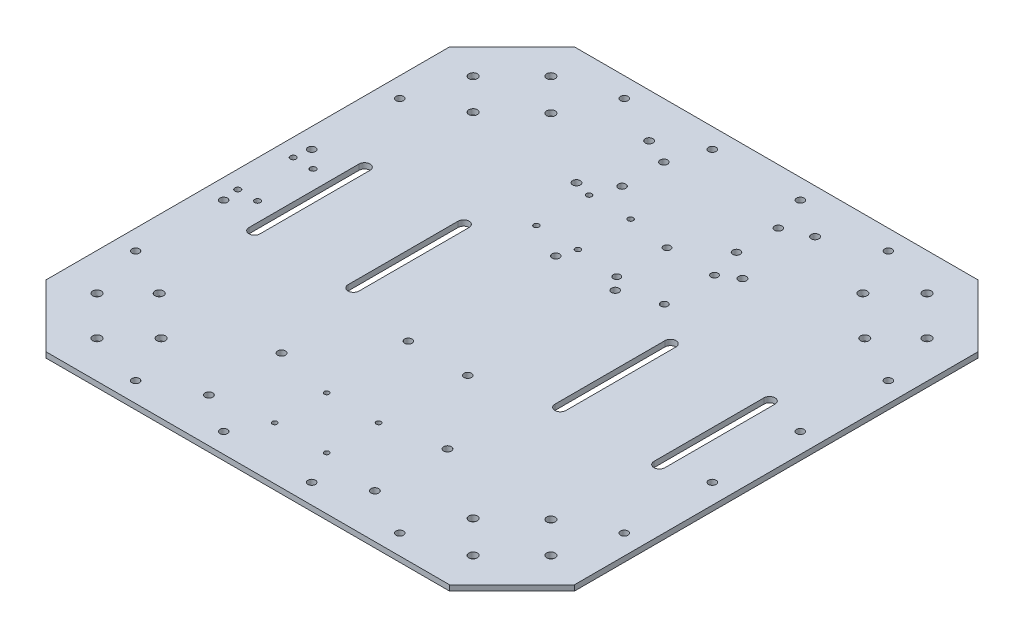
SolidWorks part; units mm, degrees
ref_plane "Front Plane" through (0, 0, 0) normal (0, 0, 1) x (1, 0, 0)
ref_plane "Top Plane" through (0, 0, 0) normal (0, 1, 0) x (1, 0, 0)
ref_plane "Right Plane" through (0, 0, 0) normal (1, 0, 0) x (0, 0, -1)
sketch "Sketch1" plane through (0, 0, 0) normal (0, 1, 0) x (1, 0, 0)
  line L0 (-61.766, 15.7353) -> (-25.845, 51.6564)
  line L1 (-61.766, 51.6564) -> (243.034, 51.6564)
  line L2 (-61.766, 51.6564) -> (-61.766, -253.1436)
  line L3 (-61.766, -253.1436) -> (243.034, -253.1436)
  line L4 (243.034, 51.6564) -> (243.034, -253.1436)
  line L5 (90.634, 95.069) -> (90.634, -294.9418) construction
  line L6 (-86.5248, -100.7436) -> (277.558, -100.7436) construction
  line L7 (243.034, 15.7353) -> (207.1129, 51.6564)
  line L8 (243.034, -217.2226) -> (207.1129, -253.1436)
  line L9 (-61.766, -217.2226) -> (-25.845, -253.1436)
  point P8 (90.634, 51.6564)
  point P11 (-61.766, -100.7436)
  point P46 (0, 0)
  dimension "D1" = 304.8
  dimension "D2" = 304.8
  dimension "D3" = 45
  dimension "D4" = 50.8
extrude "Boss-Extrude1" add sketch "Sketch1" along normal blind 3.175 contours L2 L9 L3 L8 L4 L7 L1 L0 region at (90.634, 0, 100.7436)
sketch "Sketch2" plane through (0, 3.175, 0) normal (0, 1, 0) x (1, 0, 0)
  line L0 (-40.323, 7.7627) -> (-22.3625, -10.1978) construction
  line L1 (-17.8724, 30.2133) -> (0.6409, 11.7001) construction
  line L2 (-43.8055, 33.6958) -> (20.8232, -30.9329) construction
  line L3 (-61.766, 15.7353) -> (-25.845, 51.6564) construction
  line L7 (90.634, 51.6564) -> (90.634, -253.1436) construction
  line L8 (-25.845, 51.6564) -> (207.1129, 51.6564) construction
  line L9 (-25.845, -253.1436) -> (207.1129, -253.1436) construction
  line L10 (-61.766, -100.7436) -> (243.034, -100.7436) construction
  line L11 (-61.766, 15.7353) -> (-61.766, -217.2226) construction
  line L12 (243.034, 15.7353) -> (243.034, -217.2226) construction
  circle A0 centre (-17.8724, 30.2133) radius 2.4638
  circle A1 centre (0.6409, 11.7001) radius 2.4638
  circle A2 centre (-22.3625, -10.1978) radius 2.4638
  circle A3 centre (-40.323, 7.7627) radius 2.4638
  circle A4 centre (203.6304, -10.1978) radius 2.4638
  circle A5 centre (221.5909, 7.7627) radius 2.4638
  circle A6 centre (180.627, 11.7001) radius 2.4638
  circle A7 centre (199.1403, 30.2133) radius 2.4638
  circle A8 centre (-22.3625, -191.2895) radius 2.4638
  circle A9 centre (-40.323, -209.25) radius 2.4638
  circle A10 centre (-17.8724, -231.7006) radius 2.4638
  circle A11 centre (0.6409, -213.1873) radius 2.4638
  circle A12 centre (221.5909, -209.25) radius 2.4638
  circle A13 centre (199.1403, -231.7006) radius 2.4638
  circle A14 centre (180.627, -213.1873) radius 2.4638
  circle A15 centre (203.6304, -191.2895) radius 2.4638
  dimension "D3" = 4.9276
  dimension "D4" = 4.9276
  dimension "D5" = 4.9276
  dimension "D6" = 4.9276
  dimension "D1" = 25.4
  dimension "D2" = 31.75
  dimension "D7" = 15.875
extrude "Cut-Extrude1" cut sketch "Sketch2" against normal blind 6.35
sketch "Sketch3" plane through (0, 3.175, 0) normal (0, 1, 0) x (1, 0, 0)
  line L0 (-61.766, -100.7436) -> (278.5513, -100.7436) construction
  line L2 (-61.766, 15.7353) -> (-61.766, -217.2226) construction
  line L3 (90.634, 51.6564) -> (90.634, -273.1997) construction
  line L4 (-25.845, 51.6564) -> (207.1129, 51.6564) construction
  circle A0 centre (73.362, -58.1986) radius 2.159
  circle A1 centre (107.652, -58.1986) radius 2.159
  circle A2 centre (73.362, -143.2886) radius 2.159
  circle A3 centre (107.652, -143.2886) radius 2.159
  point P10 (-61.766, -100.7436)
  dimension "D3" = 4.318
  dimension "D4" = 4.318
  dimension "D5" = 4.318
  dimension "D6" = 4.318
  dimension "D1" = 34.29
  dimension "D2" = 85.09
  dimension "D7" = 42.545
  dimension "D8" = 17.272
extrude "Cut-Extrude2" cut sketch "Sketch3" against normal blind 6.35
sketch "Sketch4" plane through (0, 3.175, 0) normal (0, 1, 0) x (1, 0, 0)
  line L0 (90.634, 51.6564) -> (90.634, -36.4614) construction
  line L1 (-25.845, 51.6564) -> (207.1129, 51.6564) construction
  line L2 (-61.766, -100.7436) -> (257.447, -100.7436) construction
  line L3 (-61.766, 15.7353) -> (-61.766, -217.2226) construction
  circle A0 centre (42.755, 26.2564) radius 2.2225
  circle A1 centre (138.513, 26.2564) radius 2.2225
  circle A2 centre (42.755, -15.6536) radius 2.2225
  circle A3 centre (138.513, -15.6536) radius 2.2225
  circle A4 centre (138.513, -185.8336) radius 2.2225
  circle A5 centre (42.755, -185.8336) radius 2.2225
  circle A6 centre (138.513, -227.7436) radius 2.2225
  circle A7 centre (42.755, -227.7436) radius 2.2225
  dimension "D1" = 4.445
  dimension "D2" = 4.445
  dimension "D3" = 4.445
  dimension "D4" = 4.445
  dimension "D5" = 95.758
  dimension "D6" = 41.91
  dimension "D7" = 47.879
  dimension "D8" = 25.4
extrude "Cut-Extrude3" cut sketch "Sketch4" against normal through all
sketch "Sketch5" plane through (0, 3.175, 0) normal (0, 1, 0) x (1, 0, 0)
  line L0 (-61.766, -100.7436) -> (105.2484, -100.7436) construction
  line L1 (-61.766, 15.7353) -> (-61.766, -217.2226) construction
  circle A0 centre (-51.606, -84.7416) radius 1.651
  circle A1 centre (-40.176, -84.7416) radius 1.651
  circle A2 centre (-40.176, -116.7456) radius 1.651
  circle A3 centre (-51.606, -116.7456) radius 1.651
  dimension "D1" = 3.302
  dimension "D2" = 3.302
  dimension "D3" = 11.43
  dimension "D4" = 16.002
  dimension "D5" = 10.16
extrude "Cut-Extrude4" cut sketch "Sketch5" against normal through all
sketch "Sketch6" plane through (0, 3.175, 0) normal (0, 1, 0) x (1, 0, 0)
  line L0 (243.034, 15.7353) -> (243.034, -217.2226) construction
  line L1 (-25.845, 51.6564) -> (207.1129, 51.6564) construction
  line L2 (90.634, 51.6564) -> (90.634, -253.1436) construction
  line L3 (-25.845, -253.1436) -> (207.1129, -253.1436) construction
  line L4 (-61.766, 15.7353) -> (-61.766, -217.2226) construction
  circle A0 centre (101.302, -22.0036) radius 2.032
  circle A1 centre (101.302, -50.9596) radius 2.032
  circle A2 centre (128.734, -50.9596) radius 2.032
  circle A3 centre (128.734, -22.0036) radius 2.032
  circle A4 centre (57.614, 19.9064) radius 2.159
  circle A5 centre (57.614, -4.2236) radius 2.159
  circle A6 centre (123.654, -4.2236) radius 2.159
  circle A7 centre (123.654, 19.9064) radius 2.159
  circle A8 centre (75.648, -192.6916) radius 1.397
  circle A9 centre (75.648, -222.6636) radius 1.397
  circle A10 centre (105.62, -222.6636) radius 1.397
  circle A11 centre (105.62, -192.6916) radius 1.397
  circle A12 centre (52.534, -18.1936) radius 1.55
  circle A13 centre (52.534, -48.5936) radius 1.55
  circle A14 centre (76.534, -18.1936) radius 1.55
  circle A15 centre (76.534, -48.5936) radius 1.55
  point P40 (0, 0)
  point P41 (0, 0)
  dimension "D1" = 4.064
  dimension "D6" = 4.318
  dimension "D7" = 4.318
  dimension "D10" = 2.794
  dimension "D11" = 2.794
  dimension "D15" = 3.1
  dimension "D16" = 3.1
  dimension "D18" = 3.1
  dimension "D19" = 3.1
  dimension "D2" = 27.432
  dimension "D3" = 28.956
  dimension "D4" = 114.3
  dimension "D5" = 73.66
  dimension "D8" = 33.02
  dimension "D9" = 24.13
  dimension "D12" = 14.986
  dimension "D13" = 29.972
  dimension "D14" = 30.48
  dimension "D17" = 30.4
  dimension "D20" = 24
  dimension "D21" = 31.75
  dimension "D22" = 114.3
  dimension "D23" = 69.85
extrude "Cut-Extrude5" cut sketch "Sketch6" against normal through all
sketch "Sketch7" plane through (0, 3.175, 0) normal (0, 1, 0) x (1, 0, 0)
  line L0 (90.634, 51.6564) -> (90.634, -272.7763) construction
  line L1 (-25.845, 51.6564) -> (207.1129, 51.6564) construction
  line L2 (-61.766, -100.7436) -> (338.9555, -100.7436) construction
  line L3 (-61.766, 15.7353) -> (-61.766, -217.2226) construction
  circle A0 centre (65.234, 40.2264) radius 2.159
  circle A1 centre (14.434, 40.2264) radius 2.159
  circle A2 centre (-50.336, -75.3436) radius 2.159
  circle A3 centre (-50.336, -24.5436) radius 2.159
  circle A4 centre (231.604, -24.5436) radius 2.159
  circle A5 centre (231.604, -75.3436) radius 2.159
  circle A6 centre (166.834, 40.2264) radius 2.159
  circle A7 centre (116.034, 40.2264) radius 2.159
  circle A8 centre (116.034, -241.7136) radius 2.159
  circle A9 centre (166.834, -241.7136) radius 2.159
  circle A10 centre (231.604, -126.1436) radius 2.159
  circle A11 centre (231.604, -176.9436) radius 2.159
  circle A12 centre (-50.336, -176.9436) radius 2.159
  circle A13 centre (-50.336, -126.1436) radius 2.159
  circle A14 centre (14.434, -241.7136) radius 2.159
  circle A15 centre (65.234, -241.7136) radius 2.159
  dimension "D1" = 4.318
  dimension "D2" = 4.318
  dimension "D6" = 4.318
  dimension "D7" = 4.318
  dimension "D3" = 25.4
  dimension "D4" = 50.8
  dimension "D5" = 11.43
  dimension "D8" = 25.4
  dimension "D9" = 50.8
  dimension "D10" = 11.43
extrude "Cut-Extrude6" cut sketch "Sketch7" against normal through all
sketch "Sketch8" plane through (0, 3.175, 0) normal (0, 1, 0) x (1, 0, 0)
  line L0 (-26.206, -68.9936) -> (-26.206, -132.4936) construction
  line L1 (-23.031, -68.9936) -> (-23.031, -132.4936)
  line L2 (-29.381, -68.9936) -> (-29.381, -132.4936)
  line L3 (30.944, -68.9936) -> (30.944, -132.4936) construction
  line L4 (34.119, -68.9936) -> (34.119, -132.4936)
  line L5 (27.769, -68.9936) -> (27.769, -132.4936)
  line L7 (243.034, 15.7353) -> (243.034, -217.2226) construction
  line L8 (90.634, 51.6564) -> (90.634, -227.3263) construction
  line L9 (-25.845, 51.6564) -> (207.1129, 51.6564) construction
  line L10 (207.474, -68.9936) -> (207.474, -132.4936) construction
  line L11 (204.299, -68.9936) -> (204.299, -132.4936)
  line L12 (210.649, -68.9936) -> (210.649, -132.4936)
  line L13 (150.324, -68.9936) -> (150.324, -132.4936) construction
  line L14 (147.149, -68.9936) -> (147.149, -132.4936)
  line L15 (153.499, -68.9936) -> (153.499, -132.4936)
  arc A0 (-23.031, -68.9936) -> (-29.381, -68.9936) centre (-26.206, -68.9936) ccw
  arc A1 (-29.381, -132.4936) -> (-23.031, -132.4936) centre (-26.206, -132.4936) ccw
  arc A2 (34.119, -68.9936) -> (27.769, -68.9936) centre (30.944, -68.9936) ccw
  arc A3 (27.769, -132.4936) -> (34.119, -132.4936) centre (30.944, -132.4936) ccw
  arc A4 (204.299, -68.9936) -> (210.649, -68.9936) centre (207.474, -68.9936) cw
  arc A5 (210.649, -132.4936) -> (204.299, -132.4936) centre (207.474, -132.4936) cw
  arc A6 (147.149, -68.9936) -> (153.499, -68.9936) centre (150.324, -68.9936) cw
  arc A7 (153.499, -132.4936) -> (147.149, -132.4936) centre (150.324, -132.4936) cw
  point P2 (-26.206, -100.7436)
  point P7 (30.944, -100.7436)
  point P14 (90.634, -87.835)
  point P17 (243.034, -100.7436)
  point P24 (207.474, -100.7436)
  point P31 (150.324, -100.7436)
  dimension "D5" = 6.35
  dimension "D1" = 63.5
  dimension "D2" = 63.5
  dimension "D3" = 50.8
  dimension "D4" = 59.69
  dimension "D6" = 6.35
extrude "Cut-Extrude8" cut sketch "Sketch8" against normal through all
